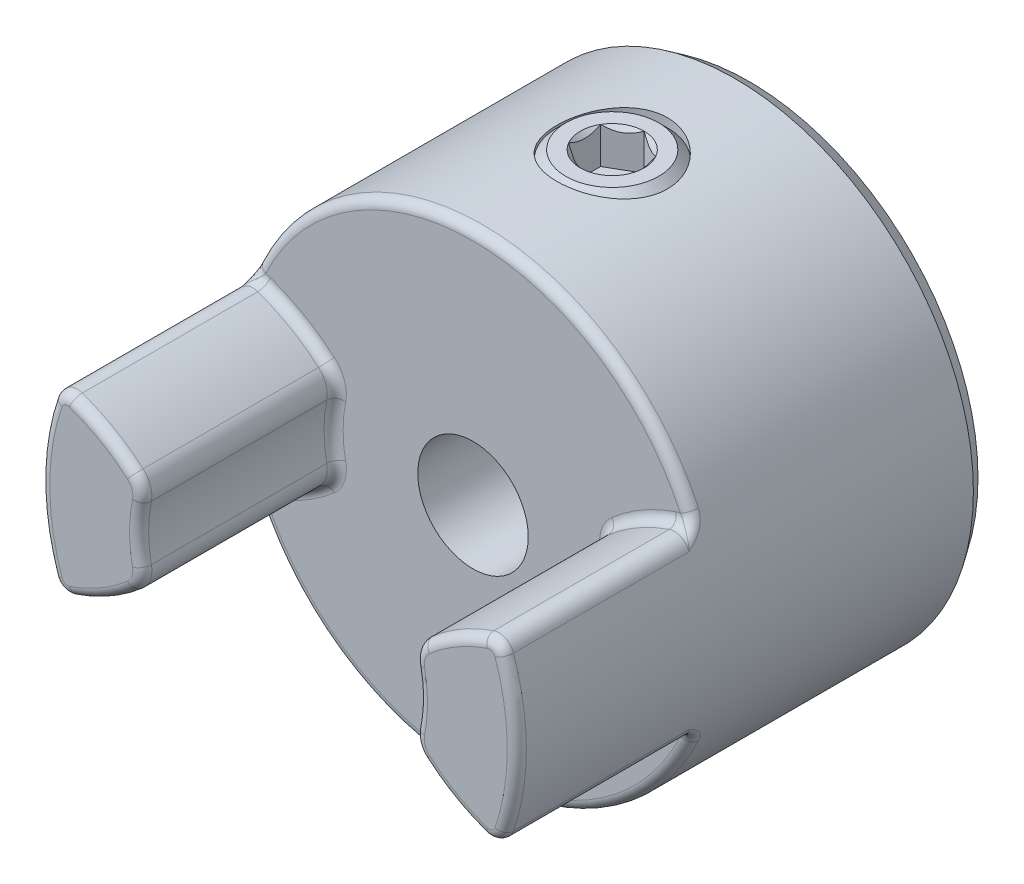
SolidWorks part; units mm, degrees
ref_plane "Front Plane" through (0, 0, 0) normal (0, 0, 1) x (1, 0, 0)
ref_plane "Top Plane" through (0, 0, 0) normal (0, 1, 0) x (1, 0, 0)
ref_plane "Right Plane" through (0, 0, 0) normal (1, 0, 0) x (0, 0, -1)
sketch "Sketch1" plane through (0, 0, 0) normal (0, 0, 1) x (1, 0, 0)
  line L0 (0, 0) -> (0, 3.175) construction
  line L4 (0, 0) -> (0, -13.6922) construction
  line L7 (0, 13.6922) -> (0, 5.7547) construction
  line L8 (3.175, 13.319) -> (3.175, 5.7547)
  line L9 (3.3125, 3.2544) -> (2.2126, 2.6194) construction
  line L10 (2.2126, 2.6194) -> (3.3125, 1.9844) construction
  line L11 (3.3125, 1.9844) -> (3.3125, 3.2544) construction
  line L12 (3.175, 3.175) -> (3.175, 2.0637) construction
  line L13 (3.3125, 2.6194) -> (3.175, 2.6194) construction
  line L14 (3.175, 2.6194) -> (2.3501, 2.6194) construction
  line L15 (2.3501, 2.6194) -> (2.2126, 2.6194) construction
  line L16 (2.3501, 2.6987) -> (2.3501, 2.54)
  line L17 (3.2437, 3.2147) -> (3.2437, 2.0241)
  line L18 (2.3501, 2.54) -> (3.2437, 2.0241)
  line L19 (2.3501, 2.6987) -> (3.2437, 3.2147)
  line L20 (0, 0) -> (13.6922, 0) construction
  circle A0 centre (0, 0) radius 13.6922
  circle A1 centre (0, 0) radius 3.175
  arc A5 (7.8541, -1.5781) -> (7.8541, 1.5781) centre (0.0103, 0) ccw
  arc A6 (7.8541, -1.5781) -> (8.3268, -2.9591) centre (9.2735, -1.8637) ccw
  arc A7 (8.3268, -2.9591) -> (11.8239, -4.9784) centre (15.3522, 5.1699) ccw
  arc A8 (11.8239, -4.9784) -> (12.9571, -4.4261) centre (12.1158, -4.1387) ccw
  arc A9 (12.9571, -4.4261) -> (12.9571, 4.4261) centre (0, 0) ccw
  arc A10 (12.9571, 4.4261) -> (11.8239, 4.9784) centre (12.1158, 4.1387) ccw
  arc A11 (11.8239, 4.9784) -> (8.3268, 2.9591) centre (15.3522, -5.1699) ccw
  arc A12 (8.3268, 2.9591) -> (7.8541, 1.5781) centre (9.2735, 1.8637) ccw
  point P8 (0, 3.175)
  point P33 (3.2437, 2.6194)
  point P48 (13.6922, 0)
  point P49 (8.0113, 0)
  dimension "OD" = 27.3844
  dimension "For Shaft Diameter" = 6.35
  dimension "D1" = 1.4478
  dimension "D3" = 8.001
  dimension "D5" = 10.7442
  dimension "D6" = 0.889
  dimension "Screw Length" = 7.9375
  dimension "D2" = 6.35
  dimension "Set Screw Pitch" = 1.27
  dimension "D4" = 0.1588
  dimension "D8" = 3.1563
  dimension "D7" = 9.9568
  dimension "D9" = 5.9182
sketch "Sketch2" plane through (0, 0, 0) normal (1, 0, 0) x (0, 0, -1)
  line L0 (13.5255, 0) -> (-30.1307, 0) construction
  circle A0 centre (5.6515, 0) radius 3.175
  point P3 (-2.3495, 0)
  point P5 (13.5255, 0)
  point P6 (-13.5255, 0)
  dimension "Screw Dia" = 6.35
  dimension "Bore Depth" = 15.875
  dimension "Lug Lg" = 11.176
  dimension "Overall Length" = 43.6562
  dimension "D1" = 13.5255
  dimension "Screw Offset" = 7.874
sketch "Sketch3" plane through (0, 0, 0) normal (0, 0, 1) x (1, 0, 0)
  circle A1 centre (0, 0) radius 13.6922 construction
  circle A2 centre (0, 0) radius 13.6922
  circle A3 centre (0, 0) radius 3.175 construction
  circle A4 centre (0, 0) radius 3.175
extrude "Boss-Extrude1" add sketch "Sketch3" against normal up to vertex (13.5255 mm away) and the other way up to vertex (2.3495 mm away) up to point (0, 0, -13.5255) other way up to point (0, 0, 2.3495)
sketch "Sketch4" plane through (0, 0, 2.3495) normal (0, 0, 1) x (1, 0, 0)
  arc A4 (12.9571, 4.4261) -> (11.8239, 4.9784) centre (12.1158, 4.1387) ccw construction
  arc A5 (12.9571, -4.4261) -> (12.9571, 4.4261) centre (0, 0) ccw construction
  arc A6 (11.8239, -4.9784) -> (12.9571, -4.4261) centre (12.1158, -4.1387) ccw construction
  arc A7 (8.3268, -2.9591) -> (11.8239, -4.9784) centre (15.3522, 5.1699) ccw construction
  arc A8 (7.8541, -1.5781) -> (8.3268, -2.9591) centre (9.2735, -1.8637) ccw construction
  arc A9 (7.8541, -1.5781) -> (7.8541, 1.5781) centre (0.0103, 0) ccw construction
  arc A10 (8.3268, 2.9591) -> (7.8541, 1.5781) centre (9.2735, 1.8637) ccw construction
  arc A11 (11.8239, 4.9784) -> (8.3268, 2.9591) centre (15.3522, -5.1699) ccw construction
  arc A12 (12.9571, 4.4261) -> (11.8239, 4.9784) centre (12.1158, 4.1387) ccw
  arc A13 (12.9571, -4.4261) -> (12.9571, 4.4261) centre (0, 0) ccw
  arc A14 (11.8239, -4.9784) -> (12.9571, -4.4261) centre (12.1158, -4.1387) ccw
  arc A15 (8.3268, -2.9591) -> (11.8239, -4.9784) centre (15.3522, 5.1699) ccw
  arc A16 (7.8541, -1.5781) -> (8.3268, -2.9591) centre (9.2735, -1.8637) ccw
  arc A17 (7.8541, -1.5781) -> (7.8541, 1.5781) centre (0.0103, 0) ccw
  arc A18 (8.3268, 2.9591) -> (7.8541, 1.5781) centre (9.2735, 1.8637) ccw
  arc A19 (11.8239, 4.9784) -> (8.3268, 2.9591) centre (15.3522, -5.1699) ccw
extrude "Boss-Extrude2" add sketch "Sketch4" along normal up to vertex (11.176 mm away) up to point (0, 0, 13.5255)
fillet "Fillet1" radius 0.5477 8 edges at (12.5053, -4.9378, 13.5255) (9.9796, -4.1345, 13.5255) (7.9037, -2.3325, 13.5255) (8.0113, 0, 13.5255) (7.9037, 2.3325, 13.5255) (9.9796, 4.1345, 13.5255) (12.5053, 4.9378, 13.5255) (13.6922, 0, 13.5255)
pattern_circular "CirPattern1" count 2 over 360 about axis through (0, 0, -13.5255) along (0, 0, 1) of "Boss-Extrude2", "Fillet1" reverse direction yes
chamfer "Chamfer1" distance 0.5477 angle 56 2 edges at (13.6922, 0, -13.5255) (3.175, 0, -13.5255) first distance on face at (3.175, 0, -13.5255)
fillet "Fillet2" radius 0.5477 16 edges at (12.5053, 4.9378, 2.3495) (9.9796, 4.1345, 2.3495) (7.9037, 2.3325, 2.3495) (8.0113, 0, 2.3495) (7.9037, -2.3325, 2.3495) (12.5053, -4.9378, 2.3495) (-12.5053, -4.9378, 2.3495) (-12.5053, 4.9378, 2.3495) (-9.9796, 4.1345, 2.3495) (-7.9037, 2.3325, 2.3495) (-8.0113, 0, 2.3495) (-7.9037, -2.3325, 2.3495) (0, 13.6922, 2.3495) (0, -13.6922, 2.3495) (9.9796, -4.1345, 2.3495) (-9.9796, -4.1345, 2.3495)
sketch "Sketch5" plane through (0, 0, 0) normal (0, 1, 0) x (1, 0, 0)
  circle A0 centre (0, 5.6515) radius 3.175
  point P3 (0, 8.8265)
extrude "Cut-Extrude1" cut sketch "Sketch5" along normal through all
ref_plane "Plane1" through (0, 13.6922, 0) normal (0, 1, 0) x (-1, 0, 0)
sketch "Sketch6" plane through (0, 13.6922, 0) normal (0, 1, 0) x (-1, 0, 0)
  circle A0 centre (0, -5.6515) radius 3.175 construction
  circle A1 centre (0, -5.6515) radius 3.175
extrude "Boss-Extrude3" add sketch "Sketch6" against normal up to vertex (7.9375 mm away) separate body up to point (0, 5.7547, 0)
sketch "Sketch7" plane through (0, 13.6922, 0) normal (0, 1, 0) x (1, 0, 0)
  line L1 (0, 7.4846) -> (-1.5875, 6.568)
  line L2 (-1.5875, 6.568) -> (-1.5875, 4.735)
  line L3 (-1.5875, 4.735) -> (0, 3.8184)
  line L4 (0, 3.8184) -> (1.5875, 4.735)
  line L5 (1.5875, 4.735) -> (1.5875, 6.568)
  line L6 (1.5875, 6.568) -> (0, 7.4846)
  circle A0 centre (0, 5.6515) radius 1.5875 construction
  dimension "D1" = 3.175
extrude "Cut-Extrude2" cut sketch "Sketch7" against normal blind 2.0955
sketch "Sketch8" plane through (0, 13.6922, 0) normal (0, 1, 0) x (1, 0, 0)
  circle A0 centre (0, 5.6515) radius 1.8331
extrude "Cut-Extrude3" cut sketch "Sketch8" against normal up to next (2.0955 mm away) draft 45
chamfer "Chamfer2" distance 0.508 angle 45 1 edges at (0, 13.6922, -2.4765)
ref_plane "Plane3" through (0, 3.175, 0) normal (0, 1, 0) x (1, 0, 0)
chamfer "Chamfer3" distance 1.0795 angle 45 1 edges at (0, 5.7547, -2.4765)
sketch "Sketch9" plane through (0, 3.175, 0) normal (0, -1, 0) x (1, 0, 0)
  circle A0 centre (0, -5.6515) radius 3.175 construction
  circle A1 centre (0, -5.6515) radius 3.175
curve "Helix/Spiral1" pitch 1.27 height 9.2472 radius 3.175 centre (0, 3.175, -5.6515) axis (0, 1, 0) start towards (1, 0, 0)
ref_plane "Plane2" through (0, 0, -5.6515) normal (0, 0, 1) x (1, 0, 0)
sketch "Sketch11" plane through (0, 0, -5.6515) normal (0, 0, 1) x (1, 0, 0)
  line L0 (2.3501, 2.6987) -> (2.3501, 2.54) construction
  line L1 (2.3501, 2.54) -> (3.2437, 2.0241) construction
  line L2 (3.2437, 3.2147) -> (3.2437, 2.0241) construction
  line L3 (2.3501, 2.6987) -> (3.2437, 3.2147) construction
  line L4 (2.3501, 2.6987) -> (2.3501, 2.54)
  line L5 (2.3501, 2.54) -> (3.2437, 2.0241)
  line L6 (3.2437, 3.2147) -> (3.2437, 2.0241)
  line L7 (2.3501, 2.6987) -> (3.2437, 3.2147)
sweep "Sweep1" add profiles "Sketch11" path "Helix/Spiral1"
sketch "Sketch12" plane through (0, 0, -5.6515) normal (0, 0, 1) x (1, 0, 0)
  line L0 (3.4925, 0) -> (0, 0)
  line L2 (0, 0) -> (0, 3.175) construction
  line L3 (0, 0) -> (0, 3.175) construction
  line L5 (0, 0) -> (0, 3.175)
  line L13 (3.175, 13.319) -> (3.175, 5.7547) construction
  line L16 (3.4925, 3.175) -> (0, 9.2242)
  line L17 (0, 9.2242) -> (0, 3.175)
  line L21 (3.4925, 0) -> (3.4925, 3.175)
  dimension "D1" = 0.3175
  dimension "D2" = 30
revolve "Cut-Revolve1" cut sketch "Sketch12" angle 360 about L3
equation "\"D1@Sketch2\"=(\"Lug Lg@Sketch2\"+\"Bore Depth@Sketch2\")/2"
equation "\"D1@Chamfer1\" = \"OD@Sketch1\" * .02"
equation "\"D1@Sketch7\"=\"screw dia@sketch2\"/2"
equation "\"D1@Cut-Extrude2\"=\"screw dia@sketch2\"*.33"
equation "\"D1@Chamfer2\"=\"screw dia@sketch2\"*.08"
equation "\"D1@Chamfer3\"=\"screw dia@sketch2\"*.17"
equation "\"D4@Helix/Spiral1\"=\"set screw pitch@sketch1\""
equation "\"D3@Helix/Spiral1\"= ( \"OD@Sketch1\" / 2 ) - ( ( \"For Shaft Diameter@Sketch1\" / 2 ) ) - \"Set Screw Pitch@Sketch1\""
equation "\"D1@Sketch12\"=\"set screw pitch@sketch1\"/4"
equation "\"D1@Fillet1\"=\"OD@Sketch1\" * .02"
equation "\"D1@Fillet2\"=\"OD@Sketch1\" * .02"
equation "\"D4@Sketch1\"=\"Set Screw Pitch@Sketch1\"/8"
